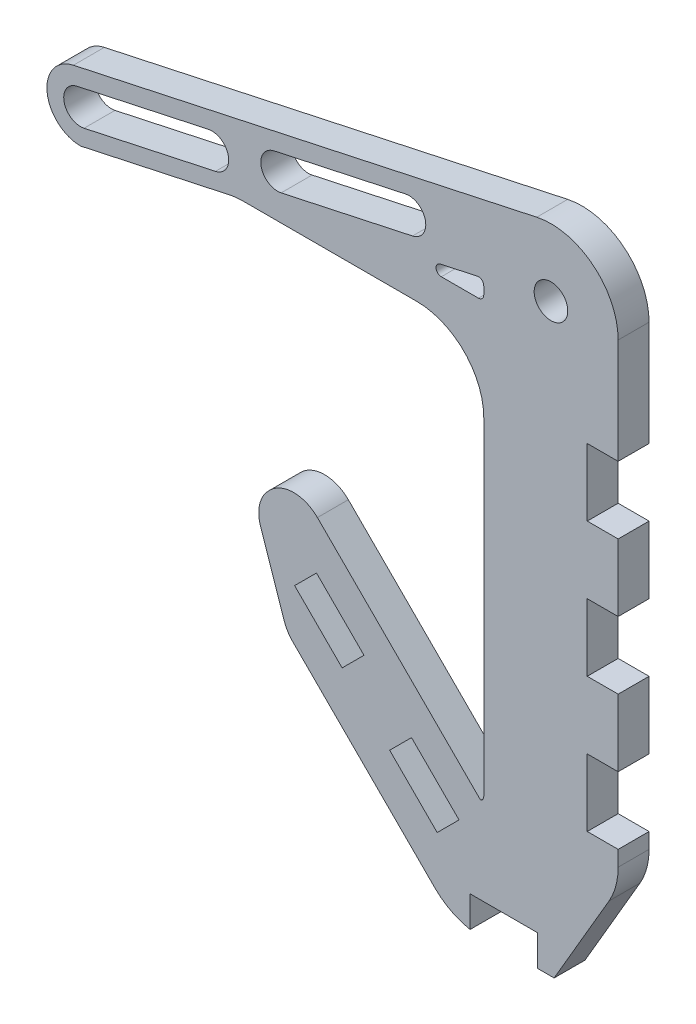
SolidWorks part; units mm, degrees
ref_plane "Front Plane" through (0, 0, 0) normal (0, 0, 1) x (1, 0, 0)
ref_plane "Top Plane" through (0, 0, 0) normal (0, 1, 0) x (1, 0, 0)
ref_plane "Right Plane" through (0, 0, 0) normal (1, 0, 0) x (0, 0, -1)
sketch "Sketch1" plane through (0, 0, 0) normal (0, 0, 1) x (1, 0, 0)
  line L0 (217.7702, 9.1265) -> (220.9452, 9.1265)
  line L1 (223.5229, 116.9897) -> (223.5229, 113.2357)
  line L2 (223.5229, 30.6857) -> (222.9299, 31.2787)
  line L3 (236.8202, 9.1265) -> (248.9229, 29.8834)
  line L4 (190.8294, 36.0673) -> (217.7702, 9.1265)
  line L5 (180.072, 59.0768) -> (187.6019, 66.6067)
  line L6 (183.471, 62.4758) -> (243.9272, 2.0196) construction
  line L7 (187.9611, 57.9856) -> (192.092, 62.1166)
  line L8 (200.8384, 45.1083) -> (204.9694, 49.2392)
  line L9 (187.9611, 57.9856) -> (200.8384, 45.1083)
  line L10 (209.8187, 36.128) -> (213.9496, 40.259)
  line L11 (218.799, 27.1478) -> (222.9299, 31.2787)
  line L12 (218.799, 27.1478) -> (209.8187, 36.128)
  line L13 (192.092, 62.1166) -> (187.6019, 66.6067)
  line L14 (213.9496, 40.259) -> (204.9694, 49.2392)
  line L15 (233.6452, 9.1265) -> (236.8202, 9.1265)
  line L16 (248.9229, 29.8834) -> (248.9229, 36.2334)
  line L17 (223.5229, 119.5857) -> (248.9229, 119.5857) construction
  line L18 (223.5229, 106.8857) -> (147.3229, 106.8857) construction
  line L19 (233.5424, 131.9996) -> (145.9826, 113.0926)
  line L20 (147.3229, 100.5357) -> (176.7303, 106.8857)
  line L21 (206.1377, 113.2357) -> (223.5229, 113.2357)
  line L22 (176.7303, 106.8857) -> (223.5229, 106.8857)
  line L23 (206.1377, 113.2357) -> (223.5229, 116.9897)
  line L24 (223.5229, 106.8857) -> (223.5229, 30.6857)
  line L25 (147.3229, 106.8857) -> (240.0259, 126.9032) construction
  line L26 (147.3229, 106.8857) -> (172.1507, 112.2468) construction
  line L27 (146.6528, 109.9891) -> (171.4805, 115.3502)
  line L28 (147.993, 103.7822) -> (172.8208, 109.1433)
  line L29 (184.5646, 114.9273) -> (209.3923, 120.2884) construction
  line L30 (183.8944, 118.0308) -> (208.7222, 123.3919)
  line L31 (185.2347, 111.8239) -> (210.0625, 117.185)
  line L32 (190.8294, 36.0673) -> (186.3393, 40.5574)
  line L33 (233.6452, 14.9685) -> (220.9452, 14.9685)
  line L34 (233.6452, 14.9685) -> (233.6452, 9.1265)
  line L35 (248.9229, 48.9334) -> (248.9229, 61.6334)
  line L36 (220.9452, 14.9685) -> (220.9452, 9.1265)
  line L37 (227.2952, 9.1265) -> (227.2952, 14.9685) construction
  line L38 (233.6452, 12.0475) -> (220.9452, 12.0475) construction
  line L39 (186.3393, 40.5574) -> (180.072, 59.0768)
  line L40 (243.0809, 36.2334) -> (248.9229, 36.2334)
  line L41 (243.0809, 36.2334) -> (243.0809, 48.9334)
  line L42 (243.0809, 48.9334) -> (248.9229, 48.9334)
  line L43 (243.0809, 74.3334) -> (248.9229, 74.3334)
  line L44 (246.0019, 48.9334) -> (246.0019, 36.2334) construction
  line L45 (243.0809, 42.5834) -> (248.9229, 42.5834) construction
  line L46 (243.0809, 61.6334) -> (243.0809, 74.3334)
  line L47 (243.0809, 61.6334) -> (248.9229, 61.6334)
  line L48 (243.0809, 99.7334) -> (248.9229, 99.7334)
  line L49 (243.0809, 87.0334) -> (243.0809, 99.7334)
  line L50 (243.0809, 87.0334) -> (248.9229, 87.0334)
  line L51 (248.9229, 74.3334) -> (248.9229, 87.0334)
  line L52 (248.9229, 99.7334) -> (248.9229, 119.5857)
  arc A0 (248.9229, 119.5857) -> (233.5424, 131.9996) centre (236.2229, 119.5857) ccw
  circle A1 centre (236.2229, 119.5857) radius 3.175
  arc A2 (145.9826, 113.0926) -> (147.3229, 100.5357) centre (147.3229, 106.8857) ccw
  arc A3 (146.6528, 109.9891) -> (147.993, 103.7822) centre (147.3229, 106.8857) ccw
  arc A4 (172.8208, 109.1433) -> (171.4805, 115.3502) centre (172.1507, 112.2468) ccw
  arc A5 (183.8944, 118.0308) -> (185.2347, 111.8239) centre (184.5646, 114.9273) ccw
  arc A6 (210.0625, 117.185) -> (208.7222, 123.3919) centre (209.3923, 120.2884) ccw
  point P31 (159.7368, 109.5662)
  point P38 (227.2952, 12.0475)
  point P39 (196.9785, 117.6079)
  point P49 (246.0019, 42.5834)
  dimension "D5" = 25.4
  dimension "D11" = 76.2
  dimension "D13" = 12.7
  dimension "D15" = 3.175
  dimension "D1" = 50.8
  dimension "D2" = 25.4
  dimension "D3" = 45
  dimension "D4" = 38.1
  dimension "D6" = 5.842
  dimension "D7" = 6.35
  dimension "D10" = 88.9
  dimension "D12" = 12.7
  dimension "D14" = 6.35
  dimension "D16" = 25.4
  dimension "D18" = 5.842
  dimension "D19" = 12.7
  dimension "D20" = 6.35
  dimension "D21" = 19.05
  dimension "D22" = 9.525
  dimension "D23" = 5.842
  dimension "D24" = 12.7
  dimension "D25" = 12.7
  dimension "D8" = 12.7
  dimension "D9" = 12.7
  dimension "D17" = 2
  dimension "D26" = 3
extrude "Boss-Extrude1" add sketch "Sketch1" along normal blind 5.842
fillet "Fillet3" radius 12.7 4 edges at (223.5229, 106.8857, 2.921) (176.7303, 106.8857, 2.921) (248.9229, 29.8834, 2.921) (217.7702, 9.1265, 2.921)
fillet "Fillet4" radius 1 3 edges at (223.5229, 113.2357, 2.921) (223.5229, 116.9897, 2.921) (206.1377, 113.2357, 2.921)
fillet "Fillet5" radius 1 1 edges at (223.5229, 30.6857, 2.921)
sketch "Sketch4" plane through (0, 0, 5.842) normal (0, 0, 1) x (1, 0, 0)
  line L0 (192.092, 62.1166) -> (222.5908, 31.6177)
  line L1 (222.5908, 31.6177) -> (222.9299, 31.2787)
  line L2 (222.9299, 31.2787) -> (218.799, 27.1478)
  line L3 (218.799, 27.1478) -> (187.9611, 57.9856)
  line L4 (200.8384, 45.1083) -> (187.9611, 57.9856) construction
  line L5 (187.9611, 57.9856) -> (192.092, 62.1166) construction
  line L6 (187.9611, 57.9856) -> (192.092, 62.1166)
extrude "Boss-Extrude2" add sketch "Sketch4" against normal up to surface (5.842 mm away) up to face at (159.7368, 109.5662, 0)
sketch "Sketch5" plane through (0, 0, 5.842) normal (0, 0, 1) x (1, 0, 0)
  line L0 (180.8667, 59.8715) -> (230.7534, 9.9848) construction
  line L1 (187.6019, 66.6067) -> (180.072, 59.0768) construction
  line L2 (222.9299, 31.2787) -> (187.6019, 66.6067) construction
  line L3 (191.9124, 52.9567) -> (187.7815, 48.8258)
  line L4 (200.8927, 43.9764) -> (196.7617, 39.8455)
  line L5 (196.7617, 39.8455) -> (187.7815, 48.8258)
  line L6 (200.8927, 43.9764) -> (191.9124, 52.9567)
  line L7 (209.8729, 34.9962) -> (205.742, 30.8653)
  line L8 (214.7223, 21.885) -> (205.742, 30.8653)
  line L9 (218.8532, 26.0159) -> (209.8729, 34.9962)
  line L10 (218.8532, 26.0159) -> (214.7223, 21.885)
  point P9 (189.8469, 50.8912)
  dimension "D1" = 5.842
  dimension "D3" = 12.7
  dimension "D5" = 9.525
  dimension "D2" = 12.7
  dimension "D4" = 2
extrude "Cut-Extrude1" cut sketch "Sketch5" against normal through all
fillet "Fillet6" radius 6.35 3 edges at (187.6019, 66.6067, 2.921) (186.3393, 40.5574, 2.921) (180.072, 59.0768, 2.921)
